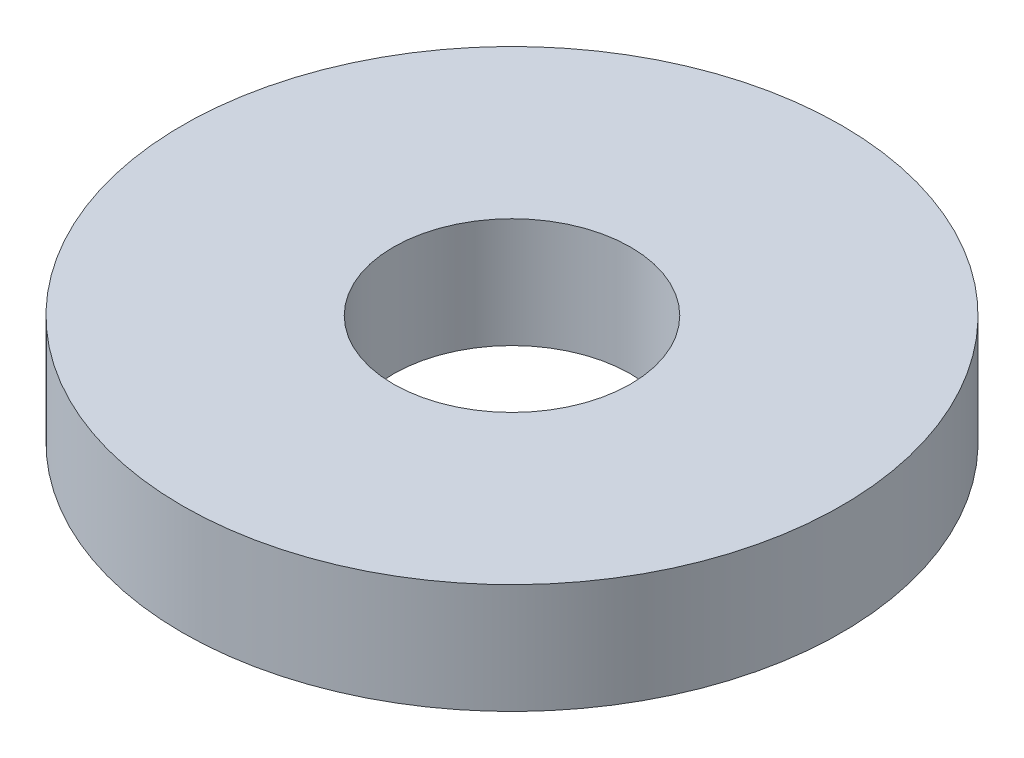
SolidWorks part; units mm, degrees
ref_plane "前基準面" through (0, 0, 0) normal (0, 0, 1) x (1, 0, 0)
ref_plane "上基準面" through (0, 0, 0) normal (0, 1, 0) x (1, 0, 0)
ref_plane "右基準面" through (0, 0, 0) normal (1, 0, 0) x (0, 0, -1)
ref_axis "基準軸1" through (0, -55, 0) along (0, 1, 0)
ref_axis "基準軸2" through (-88.99, 0, 0) along (1, 0, 0)
ref_axis "基準軸3" through (0, 0, 55) along (0, 0, -1)
sketch "草圖1" plane through (0, 0, 0) normal (0, 1, 0) x (1, 0, 0)
  circle A0 centre (0, 0) radius 2.7
  circle A1 centre (0, 0) radius 7.5
  dimension "D1" = 5.4
  dimension "D2" = 15
extrude "填料-伸長1" add sketch "草圖1" along normal blind 2.5
